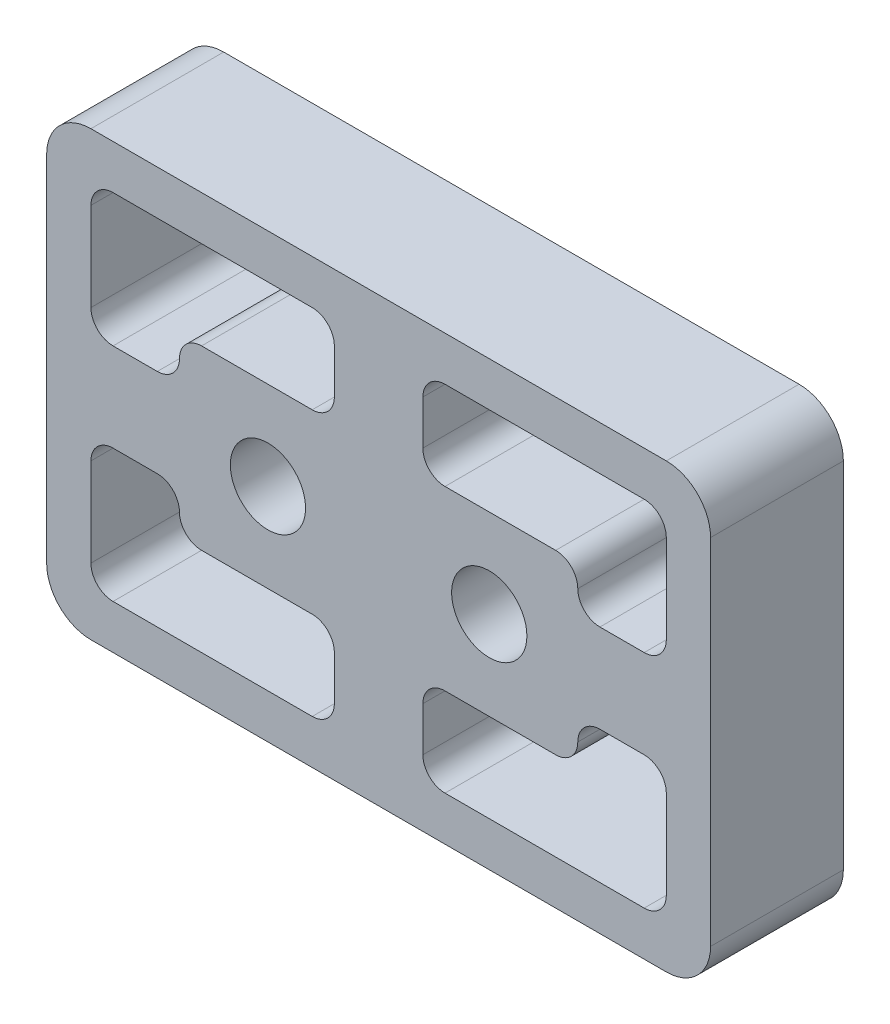
SolidWorks part; units mm, degrees
ref_plane "前视基准面" through (0, 0, 0) normal (0, 0, 1) x (1, 0, 0)
ref_plane "上视基准面" through (0, 0, 0) normal (0, 1, 0) x (1, 0, 0)
ref_plane "右视基准面" through (0, 0, 0) normal (1, 0, 0) x (0, 0, -1)
sketch "草图1" plane through (0, 0, 0) normal (0, 0, 1) x (1, 0, 0)
  line L1 (-15, -10) -> (15, -10)
  line L2 (-15, -10) -> (-15, 10)
  line L3 (-15, 10) -> (15, 10)
  line L4 (15, -10) -> (15, 10)
  line L5 (-15, -10) -> (15, 10) construction
  line L6 (-15, 10) -> (15, -10) construction
  point P0 (0, 0)
  dimension "D1" = 20
  dimension "D2" = 30
extrude "凸台-拉伸1" add sketch "草图1" along normal blind 6
fillet "圆角1" radius 2 4 edges at (-15, -10, 3) (15, -10, 3) (15, 10, 3) (-15, 10, 3)
sketch "草图2" plane through (0, 0, 6) normal (0, 0, 1) x (1, 0, 0)
  line L0 (0, 0) -> (50000, 0) construction
  line L1 (0, 0) -> (0, 50000) construction
  circle A0 centre (5, 0) radius 1.7
  circle A1 centre (-5, 0) radius 1.7
  dimension "D1" = 3.4
  dimension "D2" = 10
extrude "切除-拉伸1" cut sketch "草图2" against normal through all
sketch "草图3" plane through (0, 0, 6) normal (0, 0, 1) x (1, 0, 0)
  line L0 (-13, 2) -> (-13, 8)
  line L3 (9, 2) -> (13, 2)
  line L4 (0, 0) -> (50000, 0) construction
  line L5 (0, 0) -> (0, 50000) construction
  line L6 (-13, 8) -> (-2, 8)
  line L9 (-2, 8) -> (-2, 4)
  line L12 (9, 4) -> (9, 2)
  line L13 (-2, 4) -> (-9, 4)
  line L16 (-9, 4) -> (-9, 2)
  line L17 (-9, 2) -> (-13, 2)
  line L18 (-15, 8) -> (-15, -8) construction
  line L19 (13, 10) -> (-13, 10) construction
  line L20 (2, 4) -> (9, 4)
  line L21 (2, 8) -> (2, 4)
  line L22 (13, 8) -> (2, 8)
  line L23 (13, 2) -> (13, 8)
  line L24 (13, -2) -> (13, -8)
  line L25 (13, -8) -> (2, -8)
  line L26 (2, -8) -> (2, -4)
  line L27 (2, -4) -> (9, -4)
  line L28 (-9, -2) -> (-13, -2)
  line L29 (-9, -4) -> (-9, -2)
  line L30 (-2, -4) -> (-9, -4)
  line L31 (9, -4) -> (9, -2)
  line L32 (-2, -8) -> (-2, -4)
  line L33 (-13, -8) -> (-2, -8)
  line L34 (9, -2) -> (13, -2)
  line L35 (-13, -2) -> (-13, -8)
  dimension "D3" = 4
  dimension "D1" = 2
  dimension "D2" = 2
  dimension "D5" = 2
  dimension "D6" = 2
extrude "切除-拉伸2" cut sketch "草图3" against normal through all
fillet "圆角2" radius 1 24 edges at (-2, -4, 3) (2, 8, 3) (13, 8, 3) (13, 2, 3) (2, 4, 3) (9, 2, 3) (9, 4, 3) (13, -2, 3) (2, -8, 3) (2, -4, 3) (9, -2, 3) (9, -4, 3) (13, -8, 3) (-2, -8, 3) (-13, -8, 3) (-13, -2, 3) (-9, -2, 3) (-9, -4, 3) (-2, 8, 3) (-2, 4, 3) (-9, 4, 3) (-9, 2, 3) (-13, 2, 3) (-13, 8, 3)
equation "\"4。3\"=4.3483"
